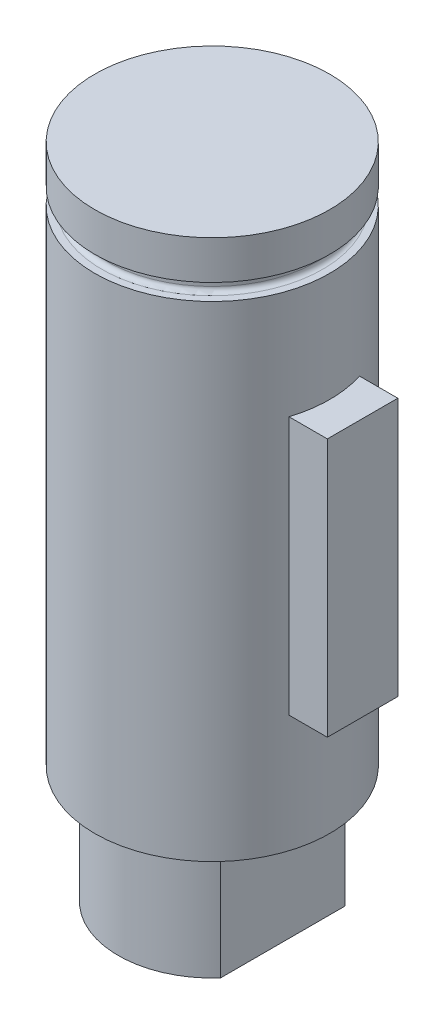
SolidWorks part; units mm, degrees
note: '?' marks a value the reader was unsure of.
ref_plane "前视基准面" through (0, 0, 0) normal (0, 0, 1) x (1, 0, 0)
ref_plane "上视基准面" through (0, 0, 0) normal (0, 1, 0) x (1, 0, 0)
ref_plane "右视基准面" through (0, 0, 0) normal (1, 0, 0) x (0, 0, -1)
sketch "Sketch1" plane through (0, 0, 0) normal (0, 1, 0) x (1, 0, 0)
  line L0 (6.4, -1.5) -> (6.4, 1.5)
  line L1 (-8.4121, 0) -> (5, 0) construction
  line L2 (6.4, 1.5) -> (4.7697, 1.5)
  line L3 (6.4, -1.5) -> (4.7697, -1.5)
  line L4 (6.4, 0) -> (13.7509, 0) construction
  arc A0 (4.7697, 1.5) -> (4.7697, -1.5) centre (0, 0) ccw
  point P8 (6.4, 0)
  dimension "D1" = 1.5
  dimension "D2" = 6.4
extrude "Boss-Extrude1" add sketch "Sketch1" along normal blind 11
sketch "Sketch2" plane through (0, 11, 0) normal (0, 1, 0) x (1, 0, 0)
  circle A0 centre (0, 0) radius 5
extrude "Boss-Extrude2" add sketch "Sketch2" along normal blind 7
sketch "Sketch3" plane through (0, 0, 0) normal (0, -1, 0) x (1, 0, 0)
  circle A0 centre (0, 0) radius 5
extrude "Boss-Extrude3" add sketch "Sketch3" along normal blind 5
sketch "Sketch4" plane through (0, -5, 0) normal (0, -1, 0) x (1, 0, 0)
  circle A0 centre (0, 0) radius 1.5
extrude "Cut-Extrude1" cut sketch "Sketch4" against normal blind 5
ref_plane "Plane6" through (0, 16, 0) normal (0, 1, 0) x (1, 0, 0)
sketch3d "3DSketch1"
  point P0 (4.9086, 4.7699, 0.9517)
ref_axis "Axis1" through (0, 18, 0) along (0, -1, 0)?
ref_plane "Plane5" through (0, 0, 0) normal (-0.1903, 0, 0.9817) x (-0.4291, -0.8994, -0.0832)
sketch "Groove Sketch" plane through (2.6251, 11.4224, 0.509) normal (-0.1903, 0, 0.9817) x (-0.883, 0.4371, -0.1712)
  line L0 (8.7861, -1.2086) -> (10.0228, -0.6075)
  line L1 (10.0228, -0.6075) -> (9.7168, 0.022)
  line L2 (9.7168, 0.022) -> (8.4801, -0.579)
  line L3 (8.3877, -0.8463) -> (8.5188, -1.1161)
  line L4 (22.0941, -39.343) -> (-17.2205, 41.5498) construction
  line L5 (0.7831, -6.9326) -> (9.7772, -2.5615) construction
  line L6 (5.2802, -4.7471) -> (-4.7736, 15.9392) construction
  arc A0 (8.5188, -1.1161) -> (8.7861, -1.2086) centre (8.6987, -1.0287) ccw
  arc A1 (8.3877, -0.8463) -> (8.4801, -0.579) centre (8.5675, -0.7589) cw
  point P10 (8.4532, -0.9812)
  dimension "Radius" = 0.2
  dimension "ID" = 9
  dimension "OD" = 12.15
  dimension "Width" = 0.7
  dimension "Location" = 2
revolve "Retaining Ring Groove" cut sketch "Groove Sketch" angle 360 about L4 reverse direction yes
other "c-ring<1>"
sketch "Sketch5" plane through (0, -5, 0) normal (0, -1, 0) x (1, 0, 0)
  line L0 (3, 1.4724) -> (3, -1.129) construction
  line L8 (3, -2.6458) -> (3, 2.6458)
  circle A1 centre (0, 0) radius 1.5
  arc A2 (3, 2.6458) -> (3, -2.6458) centre (0, 0) ccw
  dimension "D1" = 3
extrude "Boss-Extrude4" add sketch "Sketch5" along normal blind 5
